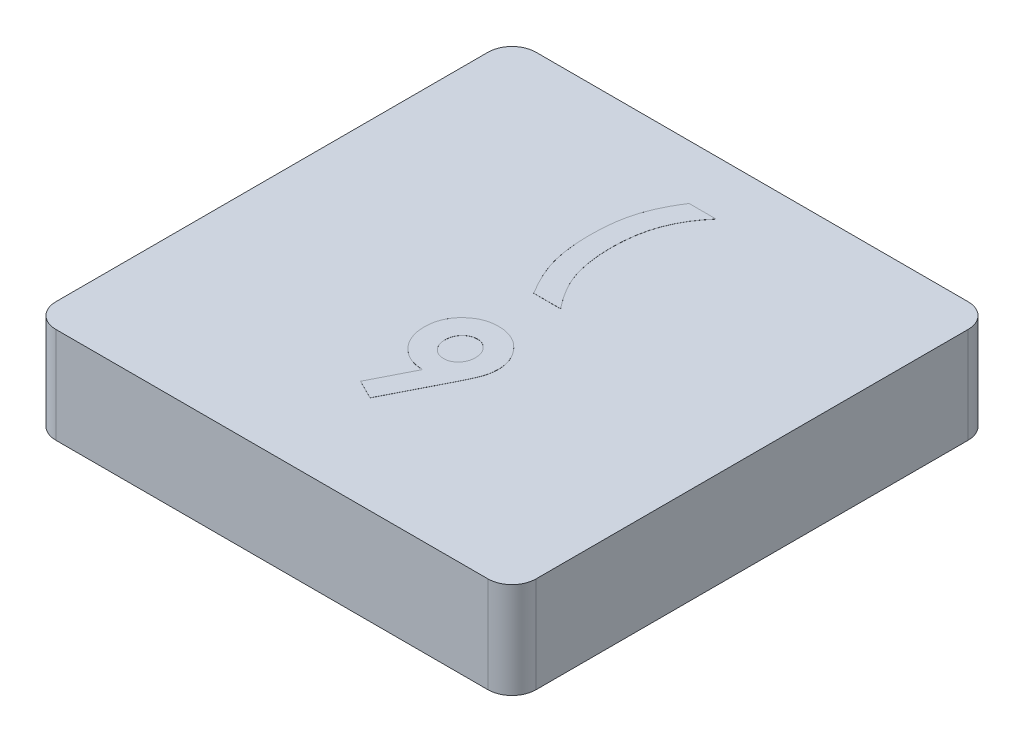
SolidWorks part; units mm, degrees
ref_plane "Front Plane" through (0, 0, 0) normal (0, 0, 1) x (1, 0, 0)
ref_plane "Top Plane" through (0, 0, 0) normal (0, 1, 0) x (1, 0, 0)
ref_plane "Right Plane" through (0, 0, 0) normal (1, 0, 0) x (0, 0, -1)
sketch "Sketch1" plane through (0, 0, 0) normal (0, 1, 0) x (1, 0, 0)
  line L0 (0, 0) -> (12.7, 0)
  line L1 (12.7, 0) -> (12.7, 12.7)
  line L2 (12.7, 12.7) -> (0, 12.7)
  line L3 (0, 12.7) -> (0, 0)
  dimension "D1" = 12.7
  dimension "D2" = 12.7
extrude "Boss-Extrude1" add sketch "Sketch1" along normal blind 2.54
fillet "Fillet1" radius 0.635 4 edges at (0, 1.27, -12.7) (12.7, 1.27, -12.7) (12.7, 1.27, 0) (0, 1.27, 0)
shell "Shell1" thickness 0.635 removed face at (6.35, 0, -6.35)
sketch "Sketch2" plane through (0, 1.905, 0) normal (0, -1, 0) x (-1, 0, 0)
  line L0 (-0.635, 6.35) -> (-12.065, 6.35) construction
  line L1 (-0.635, 12.065) -> (-0.635, 0.635) construction
  line L2 (-12.065, 0.635) -> (-12.065, 12.065) construction
  line L3 (-6.35, 0.635) -> (-6.35, 12.065) construction
  line L4 (-0.635, 0.635) -> (-12.065, 0.635) construction
  line L5 (-12.065, 12.065) -> (-0.635, 12.065) construction
  circle A0 centre (-6.35, 6.35) radius 2.54
  dimension "D1" = 5.08
extrude "Boss-Extrude2" add sketch "Sketch2" along normal up to surface (1.905 mm away) up to face at (6.35, 0, -6.35)
sketch "Sketch4" plane through (0, 2.54, 0) normal (0, 1, 0) x (1, 0, 0)
  line L0 (0, 12.065) -> (0, 0.635) construction
  line L1 (12.065, 12.7) -> (0.635, 12.7) construction
  line L2 (0.635, 0) -> (12.065, 0) construction
  text T0 "<b>9</b>"
  text T1 "<b>(</b>"
  dimension "D1" = 5.334
  dimension "D2" = 5.207
  dimension "D3" = 4.699
  dimension "D4" = 2.667
extrude "Boss-Extrude4" add sketch "Sketch4" along normal blind 0.0025
